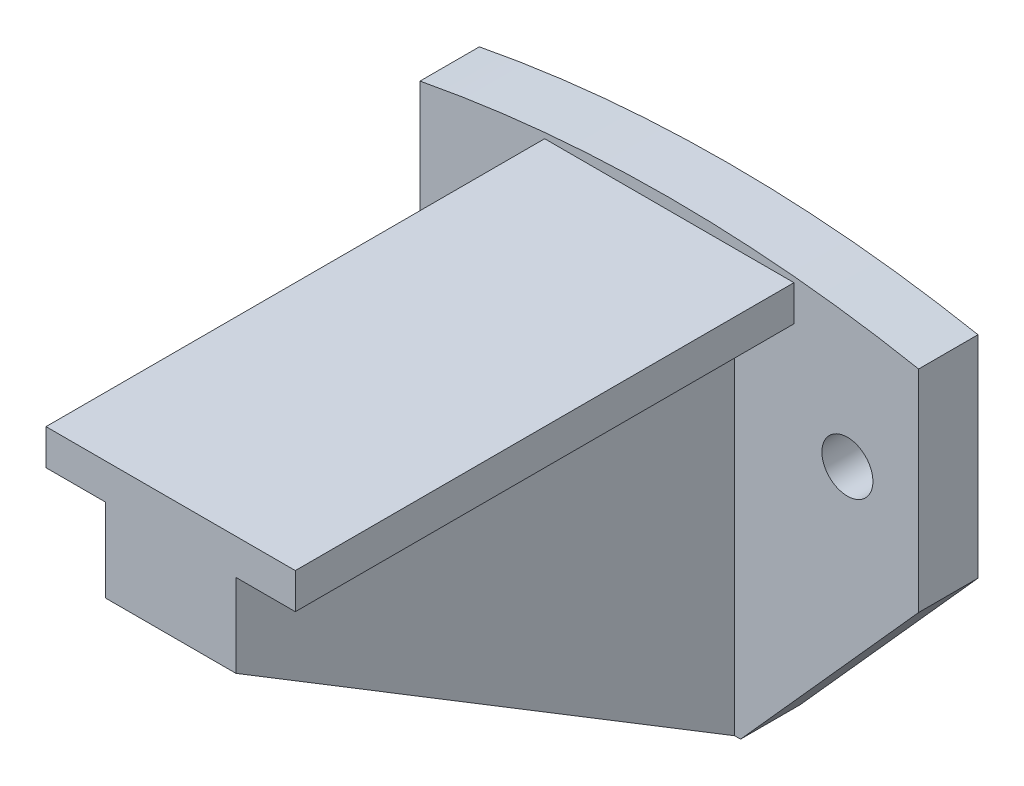
SolidWorks part; units mm, degrees
ref_plane "前视基准面" through (0, 0, 0) normal (0, 0, 1) x (1, 0, 0)
ref_plane "上视基准面" through (0, 0, 0) normal (0, 1, 0) x (1, 0, 0)
ref_plane "右视基准面" through (0, 0, 0) normal (1, 0, 0) x (0, 0, -1)
sketch "Sketch1" plane through (0, 0, 0) normal (0, 0, 1) x (1, 0, 0)
  line L0 (-8.8, 3) -> (-6.0022, -3)
  line L1 (-8.8, 3) -> (8.8, 3)
  line L3 (-6.0022, -3) -> (6.0022, -3)
  line L5 (-8.8, 3) -> (8.8, -3) construction
  line L6 (-8.8, -3) -> (8.8, 3) construction
  line L7 (8.8, 3) -> (6.0022, -3)
  point P0 (0, 0)
  dimension "D1" = 17.6
  dimension "D2" = 6
  dimension "D3" = 65
  dimension "D4" = 65
extrude "Boss-Extrude1" add sketch "Sketch1" along normal blind 42
sketch "Sketch2" plane through (0, 0, 0) normal (0, 0, -1) x (-1, 0, 0)
  line L0 (6.0022, -3) -> (-6.0022, -3) construction
  line L1 (0, 6.7593) -> (0, -103.2407) construction
  line L2 (-8.8, 3) -> (8.8, 3) construction
  line L3 (21, 4.7362) -> (21, -13.75)
  line L4 (21, -13.75) -> (-21, -13.75)
  line L5 (-21, -13.75) -> (-21, 4.7362)
  line L7 (0, 3) -> (0, -13.75) construction
  circle A0 centre (0, -103.2407) radius 110 construction
  arc A1 (21, 4.7362) -> (-21, 4.7362) centre (0, -103.2407) ccw
  line M1 (8.8, 3) -> (-8.8, 3)
  line M2 (-8.8, 3) -> (-6.0022, -3)
  line M3 (-6.0022, -3) -> (6.0022, -3)
  line M4 (6.0022, -3) -> (8.8, 3)
  dimension "D3" = 110
  dimension "D5" = 21
  dimension "D6" = 220
  dimension "D1" = 10.75
  dimension "D2" = 18.4862
  dimension "D4" = 42
extrude "Boss-Extrude3" add sketch "Sketch2" along normal blind 5 contours L7 M1 M2 M3 | L7 M1 M3 M4 | L4 L3 A1 L5 M1 M4 M3 M2 region at (0, -4.3007, 0) region at (0, 0.189, 0)
sketch "Sketch3" plane through (0, 0, 0) normal (0, 0, 1) x (1, 0, 0)
  line L0 (39.2973, 3) -> (-31.6989, 3)
  line L5 (39.2973, 3) -> (2.6938, 22.2803)
  line L6 (2.6938, 22.2803) -> (-31.6989, 3)
extrude "Cut-Extrude3" [suppressed] cut sketch "Sketch3" against normal blind 5
ref_plane "Plane1" through (0, 0, 0) normal (-1, 0, 0) x (0, 0, 1)
sketch "Sketch5" plane through (0, 0, -5) normal (0, 0, -1) x (-1, 0, 0)
  line L1 (21, -13.75) -> (-21, -13.75) construction
  line L2 (0, 6.7593) -> (0, -103.2407) construction
  line L3 (-15, -4.3721) -> (15, -4.3721) construction
  line L5 (15, -4.3721) -> (15, -13.75) construction
  line L6 (-15, -4.3721) -> (-15, -13.75) construction
  circle A0 centre (0, -103.2407) radius 100 construction
  circle A1 centre (-15, -4.3721) radius 2.15
  arc A2 (21, 4.7362) -> (-21, 4.7362) centre (0, -103.2407) ccw construction
  circle A3 centre (15, -4.3721) radius 2.15
  dimension "D1" = 15
  dimension "D3" = 4.3
  dimension "D4" = 200
  dimension "D5" = 4.3
  dimension "D2" = 30
extrude "Cut-Extrude4" cut sketch "Sketch5" against normal blind 5
sketch "Sketch4" plane through (0, 0, 0) normal (-1, 0, 0) x (0, 0, 1)
  line L1 (42, -3) -> (0, -3)
  line L2 (0, -3) -> (0, -26)
  line L3 (15, -17.7857) -> (42, -3)
  line L4 (0, -26) -> (15, -26)
  line L5 (15, -26) -> (15, -17.7857)
  dimension "D1" = 15
  dimension "D2" = 23
extrude "Boss-Extrude4" add sketch "Sketch4" against normal blind 8 and the other way blind 8
sketch "Esquisse1" plane through (8, 0, 0) normal (1, 0, 0) x (0, 0, -1)
  line L0 (-42, -3) -> (0, -26)
  line L1 (0, -3) -> (-42, -3)
  line L2 (0, -26) -> (0, -3)
extrude "Boss.-Extru.1" [suppressed] add sketch "Esquisse1" along normal blind 2
sketch "Esquisse2" plane through (0, 0, 42) normal (0, 0, 1) x (1, 0, 0)
  line L1 (8.8, 3) -> (-9.5196, 3)
  line L2 (8.8, 3) -> (8.8, 2.8)
  line L3 (8.8, 2.8) -> (-9.5196, 2.8)
  line L4 (-9.5196, 3) -> (-9.5196, 2.8)
  dimension "D1" = 0.2
extrude "Enlèv. mat.-Extru.1" cut sketch "Esquisse2" against normal up to vertex (42 mm away) up to point (-8.8, 3, 0)
sketch "Esquisse4" plane through (0, -13.75, 0) normal (0, -1, 0) x (1, 0, 0)
  line L1 (21, -5) -> (-21, -5)
  line L2 (21, -5) -> (21, 0)
  line L3 (21, 0) -> (-21, 0)
  line L4 (-21, -5) -> (-21, 0)
extrude "Boss.-Extru.2" add sketch "Esquisse4" along normal blind 15
sketch "Esquisse5" plane through (0, 0, -5) normal (0, 0, -1) x (-1, 0, 0)
  line L0 (0, 6.7593) -> (0, 25.9936) construction
  line L1 (0, -23.2407) -> (0, -28.75) construction
  line L2 (21, -28.75) -> (-21, -28.75) construction
  circle A3 centre (0, -23.2407) radius 2.15
  dimension "D2" = 4.3
extrude "Enlèv. mat.-Extru.2" cut sketch "Esquisse5" against normal blind 28
sketch "Esquisse6" plane through (0, 0, -5) normal (0, 0, -1) x (-1, 0, 0)
  line L0 (21, -12.0069) -> (6, -28.75)
  line L1 (-6, -28.75) -> (-21, -28.75) construction
  line L3 (21, 4.7362) -> (21, -28.75) construction
  line L4 (21, -28.75) -> (-21, -28.75) construction
  line L6 (-6, -28.75) -> (-21, -12.0069)
  line L7 (-21, -28.75) -> (-21, 4.7362) construction
  arc A0 (21, -12.0069) -> (-21, -12.0069) centre (0, -24.2585) cw
  dimension "D1" = 15
  dimension "D2" = 12
extrude "Enlèv. mat.-Extru.3" cut sketch "Esquisse6" against normal through all and the other way through all
sketch "Esquisse7" plane through (0, 2.8, 0) normal (0, 1, 0) x (1, 0, 0)
  line L0 (8.7067, -42) -> (-8.7067, -42) construction
  line L1 (0, -42) -> (0, -40.6611)
  line L2 (0, -49) -> (0, -39.6661) construction
  line L3 (2.5, -42.179) -> (2.5, -41.679)
  line L4 (-2.5, -42.179) -> (-2.5, -41.679)
  line L5 (2.5, -41.679) -> (-2.5, -41.679)
  line L6 (-2.5, -49) -> (-2.5, -39.6661) construction
  line L7 (2.5, -49) -> (2.5, -39.6661) construction
  arc A0 (-2.5, -42.179) -> (2.5, -42.179) centre (0, -44.333) ccw
  point P0 (0, -42)
  line M1 (-8.7067, -42) -> (8.7067, -42)
  dimension "D4" = 3.3
  dimension "D1" = 7
  dimension "D5" = 0.5
  dimension "D2" = 2.5
  dimension "D3" = 2.5
extrude "Boss.-Extru.3" add sketch "Esquisse7" against normal up to vertex (5.8 mm away) contours L4 A0 L3 M1 region at (0, 2.8, 44.6031) up to point (8, -3, 42)
sketch "Esquisse9" plane through (0, 0, 0) normal (0, 0, 1) x (1, 0, 0)
  line L0 (8, -26) -> (8, -26.1466)
  line L1 (6, -28.75) -> (8, -26.1466)
  line L3 (6, -28.75) -> (-6, -28.75)
  line L4 (-6, -28.75) -> (-8, -26.3601)
  line L6 (-8, -26) -> (-8, -26.3601)
  line L7 (8, -26) -> (-8, -26)
extrude "Boss.-Extru.4" add sketch "Esquisse9" along normal up to vertex (15 mm away) up to point (8, -26, 15)
sketch "Esquisse11" plane through (0, 0, -5) normal (0, 0, -1) x (-1, 0, 0)
  line L0 (0, 6.7593) -> (0, -103.2407) construction
  line L1 (95.2628, -158.2407) -> (0, -103.2407) construction
  line L2 (-95.2628, -158.2407) -> (0, -103.2407) construction
  line L3 (-15, -4.3721) -> (15, -4.3721) construction
  circle A0 centre (-15, -4.3721) radius 2
  circle A1 centre (15, -4.3721) radius 1.9911
  circle A2 centre (0, -103.2407) radius 100 construction
  circle A10 centre (0, -103.2407) radius 80 construction
  circle A11 centre (0, -23.2407) radius 2
  circle A13 centre (78.1227, -165.6654) radius 1.9911
  circle A14 centre (93.1227, -139.6846) radius 2
  circle A15 centre (-78.1227, -165.6654) radius 2
  circle A16 centre (-93.1227, -139.6846) radius 1.9911
  point P31 (0, -103.2407)
  point P34 (0.1144, -103.1523)
  dimension "D1" = 4
  dimension "D3" = 160
  dimension "D4" = 4
  dimension "D2" = 3
sketch "Esquisse13" plane through (0, 0, 0) normal (0, 0, 1) x (1, 0, 0)
  line L0 (-8.7067, 2.8) -> (8.7067, 2.8) construction
  line L1 (8.7067, 2.8) -> (1.0288, 12.866) construction
  line L2 (1.0288, 12.866) -> (-8.7067, 2.8) construction
sketch "Esquisse14" plane through (0, 0, 0) normal (0, 0, 1) x (1, 0, 0)
  line L1 (24.1759, 27.3666) -> (-19.9064, 27.3666)
  line L2 (24.1759, 27.3666) -> (24.1759, -35.1688)
  line L3 (24.1759, -35.1688) -> (-19.9064, -35.1688)
  line L4 (-19.9064, 27.3666) -> (-19.9064, -35.1688)
extrude "Enlèv. mat.-Extru.4" cut sketch "Esquisse14" along normal blind 50
sketch "Esquisse15" plane through (0, 0, 0) normal (0, 0, 1) x (1, 0, 0)
  line L0 (-10.5, 6.8) -> (10.5, 6.8)
  line L1 (-5.5, -3.2) -> (5.5, -3.2)
  line L2 (-5.5, 3.8) -> (-10.5, 3.8)
  line L3 (10.5, 3.8) -> (5.5, 3.8)
  line L4 (-10.5, 6.8) -> (-10.5, 3.8)
  line L5 (10.5, 6.8) -> (10.5, 3.8)
  line L8 (0, 2.8) -> (0, 32.4974) construction
  line L9 (-8.7067, 2.8) -> (8.7067, 2.8) construction
  line L12 (-5.5, -3.2) -> (-5.5, 3.8)
  line L16 (5.5, 3.8) -> (5.5, -3.2)
  dimension "D1" = 21
  dimension "D2" = 3
  dimension "D9" = 11
extrude "Boss.-Extru.5" add sketch "Esquisse15" along normal blind 42
sketch "Esquisse16" plane through (5.5, 0, 0) normal (1, 0, 0) x (0, 0, -1)
  line L2 (0, -3.2) -> (0, -28.75)
  line L3 (0, -28.75) -> (-42, -3.2)
  line L4 (-42, -3.2) -> (0, -3.2)
extrude "Boss.-Extru.7" add sketch "Esquisse16" against normal up to vertex (11 mm away) up to point (-5.5, -3.2, 42)
sketch "Esquisse20" plane through (0, 0, 0) normal (0, 0, -1) x (-1, 0, 0)
  circle A0 centre (0, -23.2407) radius 2.15
extrude "Enlèv. mat.-Extru.7" cut sketch "Esquisse20" against normal blind 42
sketch "Esquisse21" plane through (0, 0, -5) normal (0, 0, -1) x (-1, 0, 0)
  line L0 (-21, 4.7362) -> (-21, 5.7547)
  line L1 (21, 4.7362) -> (21, 5.7547)
  arc A0 (21, 5.7547) -> (-21, 5.7547) centre (0, -103.2407) ccw
  arc A1 (21, 4.7362) -> (-21, 4.7362) centre (0, -103.2407) ccw
extrude "Boss.-Extru.8" add sketch "Esquisse21" against normal up to vertex (5 mm away) up to point (10.5, 6.257, 0)
